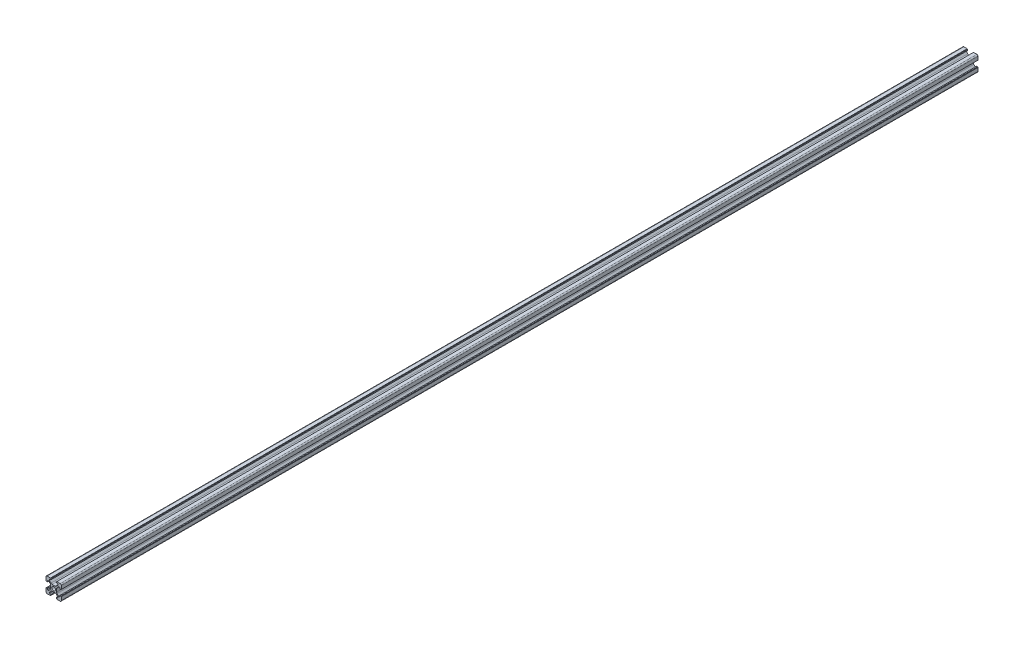
SolidWorks part; units mm, degrees
material "6063-O"
ref_plane "Front Plane" through (0, 0, 0) normal (0, 0, 1) x (1, 0, 0)
ref_plane "Top Plane" through (0, 0, 0) normal (0, 1, 0) x (1, 0, 0)
ref_plane "Right Plane" through (0, 0, 0) normal (1, 0, 0) x (0, 0, -1)
sketch "Sketch1" plane through (0, 0, 0) normal (0, 0, 1) x (1, 0, 0)
  line L0 (10, -4.1) -> (10, -8.5)
  line L1 (4.1, 10) -> (8.5, 10)
  line L2 (8.5, -10) -> (4.1, -10)
  line L3 (-8.5, -10) -> (-4.1, -10)
  line L4 (10, 8.5) -> (10, 4.1)
  line L7 (8.5, 10) -> (4.1, 10)
  line L8 (5.5, 6.5607) -> (3.4251, 4.4858)
  line L9 (8.5, 10) -> (4.1, 10)
  line L10 (3.9, 2.0109) -> (3.9, -2.0109)
  line L11 (2.0109, -3.9) -> (-2.0109, -3.9)
  line L12 (-3.9, -2.0109) -> (-3.9, 2.0109)
  line L13 (-2.0109, 3.9) -> (2.8393, 3.9)
  line L14 (2.5, 0) -> (22.2403, 0) construction
  line L15 (3.6, 9.5) -> (3.6, 8.2)
  line L16 (9.5, 3.6) -> (8.2, 3.6)
  line L17 (8.2, 3.6) -> (8.2, 5.5)
  line L18 (8.2, 5.5) -> (6.5607, 5.5)
  line L19 (10, -4.1) -> (10, -8.5)
  line L20 (4.1, 9.5) -> (3.6, 9.5)
  line L21 (4.1, 10) -> (4.1, 9.5)
  line L22 (8.5, 10) -> (4.1, 10)
  line L23 (10, 4.1) -> (9.5, 4.1)
  line L24 (9.5, 4.1) -> (9.5, 3.6)
  line L25 (5.5, 8.2) -> (5.5, 6.5607)
  line L26 (3.6, 8.2) -> (5.5, 8.2)
  line L27 (4.4858, 3.4251) -> (6.5607, 5.5)
  line L28 (10, -8.5) -> (10, -4.1)
  line L29 (6.5607, -5.5) -> (4.4858, -3.4251)
  line L30 (10, -8.5) -> (10, -4.1)
  line L31 (2.0109, -3.9) -> (-2.0109, -3.9)
  line L32 (3.9, 2.8393) -> (3.9, -2.0109)
  line L33 (9.5, -3.6) -> (8.2, -3.6)
  line L34 (3.6, -9.5) -> (3.6, -8.2)
  line L35 (3.6, -8.2) -> (5.5, -8.2)
  line L36 (5.5, -8.2) -> (5.5, -6.5607)
  line L37 (9.5, -4.1) -> (9.5, -3.6)
  line L38 (10, -4.1) -> (9.5, -4.1)
  line L39 (10, -8.5) -> (10, -4.1)
  line L40 (4.1, -10) -> (4.1, -9.5)
  line L41 (4.1, -9.5) -> (3.6, -9.5)
  line L42 (8.2, -5.5) -> (6.5607, -5.5)
  line L43 (8.2, -3.6) -> (8.2, -5.5)
  line L44 (3.4251, -4.4858) -> (5.5, -6.5607)
  line L45 (-4.1, -10) -> (-8.5, -10)
  line L46 (-10, -8.5) -> (-10, -4.1)
  line L47 (-8.5, -10) -> (-4.1, -10)
  line L48 (-5.5, -6.5607) -> (-3.4251, -4.4858)
  line L49 (-8.5, -10) -> (-4.1, -10)
  line L50 (-3.9, -2.0109) -> (-3.9, 2.0109)
  line L51 (2.0109, -3.9) -> (-2.0109, -3.9)
  line L52 (-3.6, -9.5) -> (-3.6, -8.2)
  line L53 (-9.5, -3.6) -> (-8.2, -3.6)
  line L54 (-8.2, -3.6) -> (-8.2, -5.5)
  line L55 (-8.2, -5.5) -> (-6.5607, -5.5)
  line L56 (-4.1, -9.5) -> (-3.6, -9.5)
  line L57 (-4.1, -10) -> (-4.1, -9.5)
  line L58 (-8.5, -10) -> (-4.1, -10)
  line L59 (-10, -4.1) -> (-9.5, -4.1)
  line L60 (-9.5, -4.1) -> (-9.5, -3.6)
  line L61 (-5.5, -8.2) -> (-5.5, -6.5607)
  line L62 (-3.6, -8.2) -> (-5.5, -8.2)
  line L63 (-4.4858, -3.4251) -> (-6.5607, -5.5)
  line L64 (-10, 4.1) -> (-10, 8.5)
  line L65 (-8.5, 10) -> (-4.1, 10)
  line L66 (-10, 8.5) -> (-10, 4.1)
  line L67 (-6.5607, 5.5) -> (-4.4858, 3.4251)
  line L68 (-10, 8.5) -> (-10, 4.1)
  line L69 (-2.0109, 3.9) -> (2.0109, 3.9)
  line L70 (-3.9, -2.0109) -> (-3.9, 2.0109)
  line L71 (-9.5, 3.6) -> (-8.2, 3.6)
  line L72 (-3.6, 9.5) -> (-3.6, 8.2)
  line L73 (-3.6, 8.2) -> (-5.5, 8.2)
  line L74 (-5.5, 8.2) -> (-5.5, 6.5607)
  line L75 (-9.5, 4.1) -> (-9.5, 3.6)
  line L76 (-10, 4.1) -> (-9.5, 4.1)
  line L77 (-10, 8.5) -> (-10, 4.1)
  line L78 (-4.1, 10) -> (-4.1, 9.5)
  line L79 (-4.1, 9.5) -> (-3.6, 9.5)
  line L80 (-8.2, 5.5) -> (-6.5607, 5.5)
  line L81 (-8.2, 3.6) -> (-8.2, 5.5)
  line L82 (-3.4251, 4.4858) -> (-5.5, 6.5607)
  line L83 (4.1, -10) -> (8.5, -10)
  arc A0 (2.0109, -3.9) -> (3.4251, -4.4858) centre (2.0109, -5.9) cw
  arc A1 (4.4858, -3.4251) -> (3.9, -2.0109) centre (5.9, -2.0109) cw
  arc A2 (3.9, 2.0109) -> (4.4858, 3.4251) centre (5.9, 2.0109) cw
  arc A3 (2.0109, 3.9) -> (3.4251, 4.4858) centre (2.0109, 5.9) ccw
  arc A4 (-2.0109, 3.9) -> (-3.4251, 4.4858) centre (-2.0109, 5.9) cw
  arc A5 (-4.4858, 3.4251) -> (-3.9, 2.0109) centre (-5.9, 2.0109) cw
  arc A6 (-3.4251, -4.4858) -> (-2.0109, -3.9) centre (-2.0109, -5.9) cw
  arc A7 (-3.9, -2.0109) -> (-4.4858, -3.4251) centre (-5.9, -2.0109) cw
  circle A8 centre (0, 0) radius 2.5
  arc A9 (-8.5, -10) -> (-10, -8.5) centre (-8.5, -8.5) cw
  arc A10 (-10, 8.5) -> (-8.5, 10) centre (-8.5, 8.5) cw
  arc A11 (8.5, 10) -> (10, 8.5) centre (8.5, 8.5) cw
  arc A12 (8.5, -10) -> (10, -8.5) centre (8.5, -8.5) ccw
  point P0 (0, 0)
  point P86 (0, 0)
  point P107 (10, -10)
  dimension "D3" = 2
  dimension "D5" = 5
  dimension "D2" = 1.5
  dimension "D8" = 1.5
  dimension "D6" = 4
  dimension "D7" = 6.1
  dimension "D11" = 0.5
  dimension "D12" = 0.5
extrude "Boss-Extrude2" add sketch "Sketch1" along normal blind 1200 contours L2 A12 L0 L38 L37 L33 L43 L42 L29 A1 L10 A2 L27 L18 L17 L16 L24 L23 L4 A11 L1 L21 L20 L15 L26 L25 L8 A3 L13 A4 L82 L74 L73 L72 L79 L78 L65 A10 L64 L76 L75 L71 L81 L80 L67 A5 L12 region at (9.7172, -6.3, 0)
